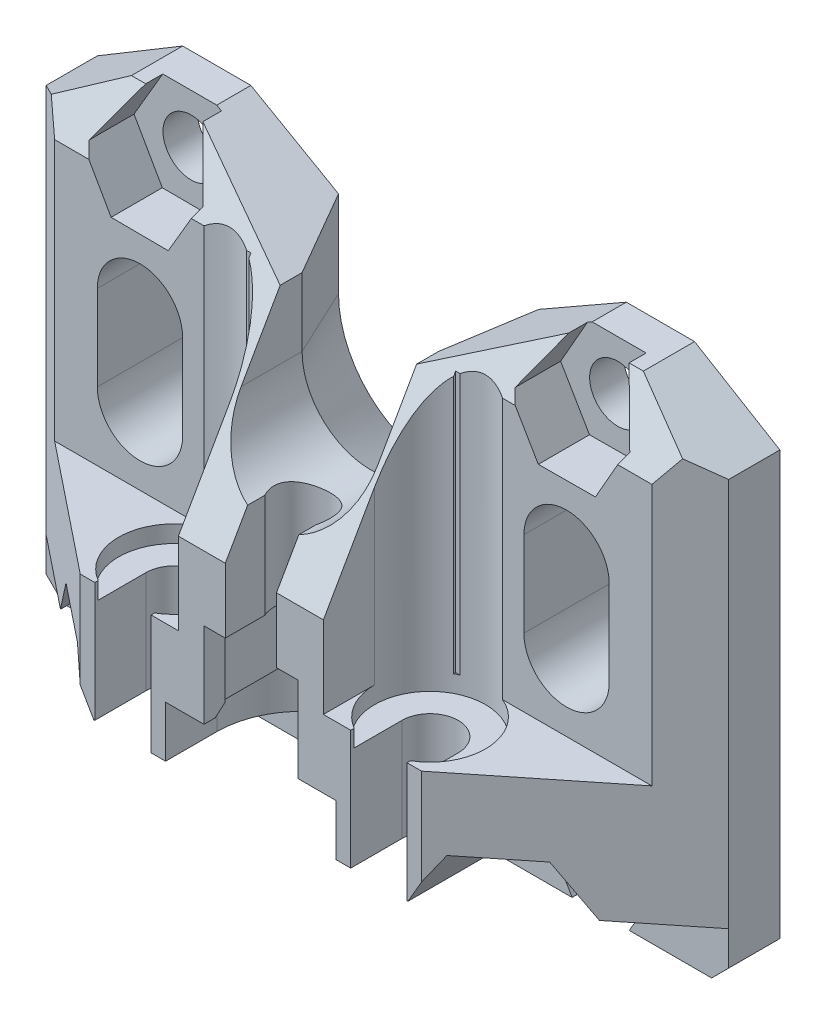
SolidWorks part; units mm, degrees
ref_plane "Front Plane" through (0, 0, 0) normal (0, 0, 1) x (1, 0, 0)
ref_plane "Top Plane" through (0, 0, 0) normal (0, 1, 0) x (1, 0, 0)
ref_plane "Right Plane" through (0, 0, 0) normal (1, 0, 0) x (0, 0, -1)
sketch "Sketch1" plane through (0, 0, 0) normal (0, 0, 1) x (1, 0, 0)
  line L1 (-20, 0) -> (20, 0)
  line L2 (-20, 0) -> (-20, 28.8)
  line L3 (-20, 28.8) -> (20, 28.8)
  line L4 (20, 0) -> (20, 28.8)
  dimension "D2" = 40
  dimension "D3" = 28.8
extrude "Boss-Extrude1" add sketch "Sketch1" along normal blind 11
chamfer "Chamfer2" distance 8 distance2 14 1 edges at (0, 28.8, 11) first distance on face at (0, 28.8, 5.5)
sketch "Sketch10" plane through (0, 0, 11) normal (0, 0, 1) x (1, 0, 0)
  line L0 (-6, 28.8) -> (-6, 10)
  line L2 (-6, 10) -> (-20, 10)
  line L3 (-20, 14.8) -> (-20, 0) construction
  line L4 (0, 0) -> (0, 29.2248) construction
  line L5 (-6, 28.8) -> (-20, 28.8)
  line L6 (-20, 28.8) -> (-20, 10)
  line L7 (20, 28.8) -> (20, 10)
  line L8 (6, 28.8) -> (20, 28.8)
  line L9 (6, 10) -> (20, 10)
  line L10 (6, 28.8) -> (6, 10)
  line L11 (-20, 28.8) -> (20, 28.8) construction
  dimension "D1" = 10
  dimension "D2" = 6
extrude "Cut-Extrude7" cut sketch "Sketch10" against normal offset from surface (6 mm away) 5 up to face at (0, 14.4, 0)
sketch "Sketch11" plane through (0, 0, 11) normal (0, 0, 1) x (1, 0, 0)
  line L0 (20, 0) -> (20, 10) construction
  line L1 (-20, 0) -> (20, 0)
  line L2 (-20, 0) -> (-20, 3)
  line L3 (-20, 3) -> (20, 3)
  line L4 (20, 0) -> (20, 3)
  dimension "D1" = 3
extrude "Cut-Extrude8" cut sketch "Sketch11" against normal blind 8
chamfer "Chamfer3" distance 8 distance2 10 2 edges at (-20, 6.5, 11) (20, 6.5, 11) first distance on face at (-20, 12.1, 4.5556) first distance on face at (20, 12.1, 4.5556)
sketch "Sketch12" plane through (0, 28.8, 0) normal (0, 1, 0) x (1, 0, 0)
  line L0 (0, 0) -> (0, -14.4613) construction
  line L1 (-4.25, -8) -> (-4.25, -11)
  line L2 (-4.25, -11) -> (-10.75, -11)
  line L3 (-10, -11) -> (-6, -11) construction
  line L4 (-10.75, -11) -> (-10.75, -8)
  line L5 (6, -11) -> (-6, -11) construction
  arc A0 (-4.25, -8) -> (-10.75, -8) centre (-7.5, -8) ccw
  dimension "D1" = 3.25
  dimension "D2" = 8
  dimension "D3" = 7.5
extrude "Cut-Extrude9" cut sketch "Sketch12" against normal up to surface (18.8 mm away) up to face at (-9.875, 10, 8)
sketch "Sketch13" plane through (0, 10, 0) normal (0, 1, 0) x (1, 0, 0)
  line L0 (-9.15, -8) -> (-9.15, -11)
  line L1 (-10, -11) -> (-4.25, -11) construction
  line L2 (-9.15, -11) -> (-5.85, -11)
  line L3 (-5.85, -8) -> (-5.85, -11)
  arc A0 (-5.85, -8) -> (-9.15, -8) centre (-7.5, -8) ccw
  arc A1 (-4.25, -8) -> (-6, -5.1169) centre (-7.5, -8) ccw construction
  dimension "D1" = 3.3
extrude "Cut-Extrude10" cut sketch "Sketch13" against normal through all
sketch "Sketch3" plane through (0, 0, 0) normal (0, -1, 0) x (1, 0, 0)
  line L0 (0, 0) -> (0, 11) construction
  line L1 (-20, 11) -> (20, 11) construction
  line L2 (-5, 8) -> (-5, 11)
  line L3 (5, 8) -> (5, 11)
  line L4 (-5, 11) -> (5, 11)
  line L5 (-20, 0) -> (20, 0) construction
  arc A0 (-5, 8) -> (5, 8) centre (0, 8) ccw
  dimension "D1" = 8
  dimension "D2" = 10
extrude "Cut-Extrude2" cut sketch "Sketch3" against normal blind 6
sketch "Sketch4" plane through (0, 0, 11) normal (0, 0, 1) x (1, 0, 0)
  line L0 (0, 28.8) -> (0, 14.0803) construction
  line L1 (20, 28.8) -> (-20, 28.8) construction
  line L2 (-4, 20.8) -> (-4, 28.8)
  line L3 (4, 20.8) -> (4, 28.8)
  line L4 (-4, 28.8) -> (4, 28.8)
  arc A0 (-4, 20.8) -> (4, 20.8) centre (0, 20.8) ccw
  dimension "D2" = 4
  dimension "D1" = 8
extrude "Cut-Extrude3" cut sketch "Sketch4" against normal through all
sketch "Sketch2" plane through (0, 0, 11) normal (0, 0, 1) x (1, 0, 0)
  line L0 (0, 0) -> (0, 28.8) construction
  line L1 (20, 28.8) -> (-20, 28.8) construction
  line L2 (-12.5, 2.9) -> (12.5, 2.9) construction
  line L3 (-12.5, 25.9) -> (12.5, 25.9) construction
  line L4 (-12.5, 25.9) -> (-12.5, 2.9) construction
  circle A0 centre (-12.5, 2.9) radius 1.65
  circle A1 centre (12.5, 2.9) radius 1.65
  circle A2 centre (12.5, 25.9) radius 1.65
  circle A3 centre (-12.5, 25.9) radius 1.65
  dimension "D5" = 3.3
  dimension "D1" = 25
  dimension "D2" = 23
  dimension "D3" = 2.9
  dimension "D4" = 12.5
extrude "Cut-Extrude1" cut sketch "Sketch2" against normal through all
sketch "Sketch5" plane through (0, 0, 11) normal (0, 0, 1) x (1, 0, 0)
  line L0 (-13.8255, 29.3763) -> (-11.1423, 29.3763)
  line L1 (-9.1514, 25.8801) -> (-11.1423, 29.3763)
  line L2 (11.1423, 29.3763) -> (13.8255, 29.3763)
  line L3 (-13.8255, 29.3763) -> (-15.8486, 25.9199)
  line L4 (-15.8486, 25.9199) -> (-14.1916, 23.01)
  line L5 (-14.1916, 23.01) -> (-10.843, 22.9901)
  line L6 (-10.843, 22.9901) -> (-9.1514, 25.8801)
  line L19 (15.8486, 25.9199) -> (13.8255, 29.3763)
  line L21 (11.1423, 29.3763) -> (9.1514, 25.8801)
  line L22 (9.1514, 25.8801) -> (10.843, 22.9901)
  line L23 (10.843, 22.9901) -> (14.1916, 23.01)
  line L24 (14.1916, 23.01) -> (15.8486, 25.9199)
  line L26 (-10.81, 28.79) -> (-14.1585, 28.8099) [skipped]
  line L27 (14.1585, 28.8099) -> (10.81, 28.79) [skipped]
  circle A0 centre (-12.5, 25.9) radius 2.9 construction
  circle A3 centre (12.5, 25.9) radius 2.9 construction
  dimension "D1" = 5.8
extrude "Cut-Extrude4" cut sketch "Sketch5" against normal offset from surface (9 mm away) 2 up to face at (-10.85, 25.9, 0)
sketch "Sketch6" plane through (0, 6, 0) normal (0, -1, 0) x (1, 0, 0)
  line L0 (0, 0) -> (0, 11) construction
  line L1 (5, 11) -> (-5, 11) construction
  line L2 (-2.75, 11) -> (2.75, 11)
  line L3 (0, 4.6514) -> (2.9, 6.3257)
  line L4 (2.9, 6.3257) -> (2.9, 9.6743)
  line L5 (-2.9, 9.6743) -> (-2.75, 9.7609)
  line L6 (2.9, 9.6743) -> (2.75, 9.7609)
  line L7 (-2.9, 9.6743) -> (-2.9, 6.3257)
  line L8 (-2.9, 6.3257) -> (0, 4.6514)
  line L9 (-2.75, 9.7609) -> (-2.75, 11)
  line L10 (0, 11.3486) -> (-2.9, 9.6743) [skipped]
  line L11 (2.9, 9.6743) -> (0, 11.3486) [skipped]
  line L12 (2.75, 9.7609) -> (2.75, 11)
  circle A0 centre (0, 8) radius 2.9 construction
  dimension "D2" = 5.8
  dimension "D3" = 5.5
  dimension "D1" = 8
extrude "Cut-Extrude5" cut sketch "Sketch6" against normal blind 5
sketch "Sketch7" plane through (0, 11, 0) normal (0, -1, 0) x (1, 0, 0)
  line L0 (0, 0) -> (0, 11) construction
  line L1 (2.75, 11) -> (-2.75, 11) construction
  line L2 (-1.5, 8.6874) -> (-1.5, 11)
  line L3 (-1.5, 11) -> (1.5, 11)
  line L4 (1.5, 11) -> (1.5, 8.6874)
  arc A0 (-1.5, 8.6874) -> (1.5, 8.6874) centre (0, 8) ccw
  dimension "D1" = 3.3
  dimension "D2" = 8
  dimension "D3" = 3
  dimension "D4" = 1.5
extrude "Cut-Extrude6" cut sketch "Sketch7" against normal through all
sketch "Sketch15" plane through (0, 10, 0) normal (0, 1, 0) x (1, 0, 0)
  circle A0 centre (-7.5, -8) radius 3.25
extrude "Cut-Extrude12" cut sketch "Sketch15" against normal blind 1
sketch "Sketch16" plane through (0, 0, 5) normal (0, 0, 1) x (1, 0, 0)
  line L0 (-12.5, 25.9) -> (-12.5, 2.9) construction
  line L1 (-15, 14) -> (-15, 19)
  line L2 (-10, 14) -> (-10, 19)
  arc A0 (-10, 19) -> (-15, 19) centre (-12.5, 19) ccw
  arc A1 (-15, 14) -> (-10, 14) centre (-12.5, 14) ccw
  dimension "D1" = 2.5
  dimension "D2" = 14
  dimension "D3" = 19
extrude "Cut-Extrude13" cut sketch "Sketch16" against normal through all
mirror "Mirror1" about plane through (0, 0, 0) normal (1, 0, 0) of "Cut-Extrude13", "Cut-Extrude10", "Cut-Extrude9", "Cut-Extrude12"
chamfer "Chamfer4" distance 3 distance2 5 1 edges at (20, 28.8, 1.5) first distance on face at (20, 12.12, 1.8)
chamfer "Chamfer5" distance 5 distance2 3 1 edges at (-20, 28.8, 1.5) first distance on face at (-12.2442, 28.8, 2)
chamfer "Chamfer6" distance 7 distance2 4 1 edges at (-4, 28.8, 1.5) tangent propagation no first distance on face at (-10.9942, 28.8, 2)
chamfer "Chamfer7" distance 4 distance2 7 1 edges at (4, 28.8, 1.5) first distance on face at (4, 24.8, 2.6429)
sketch "Sketch14" plane through (0, 0, 11) normal (0, 0, 1) x (1, 0, 0)
  line L1 (-9.1514, 2.9) -> (-10.8257, 5.8)
  line L2 (-10.8257, 5.8) -> (-14.1743, 5.8)
  line L3 (-14.1743, 5.8) -> (-15.8486, 2.9)
  line L4 (-15.8486, 2.9) -> (-14.1743, 0)
  line L5 (-14.1743, 0) -> (-10.8257, 0)
  line L6 (-10.8257, 0) -> (-9.1514, 2.9)
  line L7 (15.8486, 2.9) -> (14.1743, 5.8)
  line L8 (14.1743, 5.8) -> (10.8257, 5.8)
  line L9 (10.8257, 5.8) -> (9.1514, 2.9)
  line L10 (9.1514, 2.9) -> (10.8257, 0)
  line L11 (10.8257, 0) -> (14.1743, 0)
  line L12 (14.1743, 0) -> (15.8486, 2.9)
  circle A0 centre (-12.5, 2.9) radius 2.9 construction
  circle A1 centre (12.5, 2.9) radius 2.9 construction
  arc A2 (-14.147, 3) -> (-10.853, 3) centre (-12.5, 2.9) ccw construction
  arc A3 (10.853, 3) -> (14.147, 3) centre (12.5, 2.9) ccw construction
  dimension "D1" = 5.8
extrude "Cut-Extrude11" cut sketch "Sketch14" against normal offset from surface (9.4 mm away) 1.6 up to face at (0, 21.1667, 0)
chamfer "Chamfer8" distance 1 angle 45 2 edges at (-20, 0, 1.5) (20, 0, 1.5)
chamfer "Chamfer9" distance 0.5 angle 45 6 edges at (-2.825, 6, 9.7176) (-2.9, 6, 8) (-1.45, 6, 5.4885) (1.45, 6, 5.4885) (2.9, 6, 8) (2.825, 6, 9.7176)
chamfer "Chamfer10" distance 4 angle 25 3 edges at (-4, 22.8, 0) (0, 16.8, 0) (4, 22.8, 0) first distance on face at (-4, 22.8, 3.2143) first distance on face at (-0.0122, 18.3141, 6.25) first distance on face at (4, 22.8, 3.2143)
